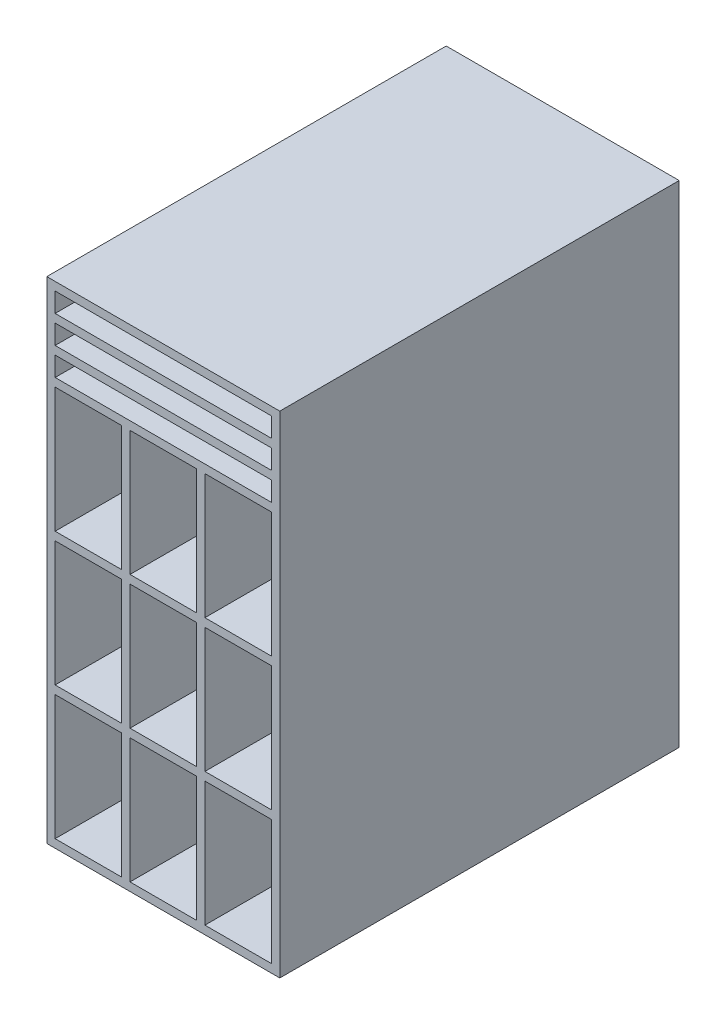
SolidWorks part; units mm, degrees
ref_plane "Front Plane" through (0, 0, 0) normal (0, 0, 1) x (1, 0, 0)
ref_plane "Top Plane" through (0, 0, 0) normal (0, 1, 0) x (1, 0, 0)
ref_plane "Right Plane" through (0, 0, 0) normal (1, 0, 0) x (0, 0, -1)
sketch "Sketch4" plane through (0, 0, 0) normal (0, 0, 1) x (1, 0, 0)
  line L1 (-177.8, -311.15) -> (177.8, -311.15)
  line L2 (-177.8, -311.15) -> (-177.8, 311.15)
  line L3 (-177.8, 311.15) -> (177.8, 311.15)
  line L4 (177.8, -311.15) -> (177.8, 311.15)
  line L5 (-177.8, -311.15) -> (177.8, 311.15) construction
  line L6 (-177.8, 311.15) -> (177.8, -311.15) construction
  point P0 (0, 0)
  dimension "D1" = 355.6
  dimension "D2" = 622.3
extrude "Boss-Extrude4" add sketch "Sketch4" along normal mid plane 190.5
shell "Shell1" thickness 12.7 removed face at (0, 0, 95.25)
sketch "Sketch5" plane through (0, 0, 95.25) normal (0, 0, 1) x (1, 0, 0)
  line L0 (-177.8, 304.8) -> (177.8, 304.8) construction
  line L1 (0, 101.6) -> (0, -101.6) construction
  line L2 (-177.8, 311.15) -> (-177.8, -311.15) construction
  line L3 (177.8, -311.15) -> (177.8, 311.15) construction
  line L6 (-177.8, -304.8) -> (177.8, -304.8) construction
  line L7 (-177.8, -311.15) -> (-177.8, -298.45) construction
  line L8 (-177.8, -311.15) -> (177.8, -311.15) construction
  line L9 (-165.1, -298.45) -> (165.1, -298.45) construction
  line L10 (-177.8, 298.45) -> (-177.8, 311.15) construction
  line L11 (165.1, 298.45) -> (-165.1, 298.45) construction
  line L12 (-171.45, -304.8) -> (-171.45, 304.8) construction
  line L13 (171.45, 304.8) -> (171.45, -304.8) construction
  line L14 (177.8, 0) -> (165.1, 0) construction
  line L15 (165.1, -298.45) -> (165.1, 298.45) construction
  line L16 (-165.1, 0) -> (-177.8, 0) construction
  line L17 (-165.1, 298.45) -> (-165.1, -298.45) construction
  line L18 (-57.15, 298.45) -> (-57.15, -298.45)
  line L19 (-165.1, -298.45) -> (165.1, -298.45) construction
  line L20 (57.15, 304.8) -> (57.15, -304.8)
  line L21 (-165.1, 101.6) -> (165.1, 101.6)
  line L22 (-165.1, -101.6) -> (165.1, -101.6)
  line L23 (-57.15, 0) -> (-171.45, 0) construction
  line L24 (-57.15, 0) -> (57.15, 0) construction
  line L25 (0, 304.8) -> (0, 101.6) construction
  point P11 (-177.8, -304.8)
  point P22 (-177.8, 304.8)
  point P30 (171.45, 0)
  point P34 (-171.45, 0)
  point P48 (0, 0)
  point P52 (0, 0)
rib "Rib1" sketch "Sketch5" sketch "Sketch5" thickness 12.7 extrusion direction normal to sketch draft on no parameters "D1"=12.7
sketch "Sketch8" plane through (0, 0, -95.25) normal (0, 0, -1) x (-1, 0, 0)
  line L4 (-177.8, -311.15) -> (177.8, -311.15)
  line L5 (177.8, -311.15) -> (177.8, 311.15)
  line L6 (177.8, 311.15) -> (-177.8, 311.15)
  line L7 (-177.8, 311.15) -> (-177.8, -311.15)
  line L8 (-177.8, -311.15) -> (177.8, -311.15)
  line L9 (177.8, -311.15) -> (177.8, 311.15)
  line L10 (177.8, 311.15) -> (-177.8, 311.15)
  line L11 (-177.8, 311.15) -> (-177.8, -311.15)
  dimension "D1" = 0
extrude "Boss-Extrude6" add sketch "Sketch8" along normal blind 76.2
shell "Shell4" thickness 12.7 removed face at (114.3, 298.45, 6.35)
sketch "Sketch9" plane through (0, 0, -171.45) normal (0, 0, -1) x (-1, 0, 0)
  line L0 (-177.8, 311.15) -> (-177.8, -311.15) construction
  line L3 (-165.1, 63.5) -> (165.1, 63.5)
  line L4 (-165.1, 63.5) -> (-165.1, -63.5)
  line L5 (-165.1, -63.5) -> (165.1, -63.5)
  line L6 (165.1, 63.5) -> (165.1, -63.5)
  line L8 (-165.1, -63.5) -> (165.1, 63.5) construction
  line L9 (-165.1, 63.5) -> (165.1, -63.5) construction
  point P10 (0, 0)
  dimension "D4" = 127
  dimension "D5" = 12.7
extrude "Cut-Extrude1" cut sketch "Sketch9" against normal blind 12.7
sketch "Sketch12" plane through (0, 0, -82.55) normal (0, 0, 1) x (1, 0, 0)
  line L2 (63.5, 241.3) -> (63.5, 165.1)
  line L4 (63.5, 298.45) -> (63.5, 107.95) construction
  arc A0 (63.5, 241.3) -> (63.5, 165.1) centre (63.5, 203.2) cw
  point P8 (63.5, 203.2)
  dimension "D1" = 38.1
extrude "Cut-Extrude3" cut sketch "Sketch12" against normal up to next
pattern_linear "LPattern1" count 3 spacing 114.3 along (-1, 0, 0) count 3 spacing 203.2 along (0, -1, 0) of "Cut-Extrude3"
sketch "Sketch16" plane through (-177.8, 0, 0) normal (1, 0, 0) x (0, 0, -1)
  line L0 (171.45, 311.15) -> (171.45, -311.15) construction
  line L1 (-95.25, -311.15) -> (171.45, -311.15) construction
  circle A0 centre (120.65, -260.35) radius 25.4
  dimension "D3" = 50.8
  dimension "D1" = 50.8
  dimension "D2" = 50.8
extrude "Cut-Extrude5" cut sketch "Sketch16" along normal up to next
sketch "Sketch6" plane through (0, 311.15, 0) normal (0, 1, 0) x (1, 0, 0)
  line L4 (-177.8, 171.45) -> (-177.8, -95.25)
  line L5 (-177.8, -95.25) -> (177.8, -95.25)
  line L6 (177.8, -95.25) -> (177.8, 171.45)
  line L7 (177.8, 171.45) -> (-177.8, 171.45)
  line L8 (-177.8, 171.45) -> (-177.8, -95.25)
  line L9 (-177.8, -95.25) -> (177.8, -95.25)
  line L10 (177.8, -95.25) -> (177.8, 171.45)
  line L12 (177.8, 171.45) -> (-177.8, 171.45)
  dimension "D1" = 0
extrude "Boss-Extrude5" add sketch "Sketch6" along normal blind 127
sketch "Sketch10" plane through (0, 0, 95.25) normal (0, 0, 1) x (1, 0, 0)
  line L0 (-177.8, 438.15) -> (177.8, 438.15) construction
  line L1 (-165.1, 425.45) -> (165.1, 425.45)
  line L2 (-165.1, 425.45) -> (-165.1, 311.15)
  line L3 (-165.1, 311.15) -> (165.1, 311.15)
  line L4 (165.1, 425.45) -> (165.1, 311.15)
  line L5 (-177.8, 438.15) -> (-177.8, -311.15) construction
  line L6 (177.8, -311.15) -> (177.8, 438.15) construction
  line L7 (165.1, 298.45) -> (63.5, 298.45) construction
  dimension "D1" = 12.7
  dimension "D2" = 12.7
  dimension "D3" = 12.7
  dimension "D4" = 12.7
extrude "Cut-Extrude2" cut sketch "Sketch10" against normal offset from surface (254 mm away) 12.7 up to face at (0, 0, -171.45)
sketch "Sketch13" plane through (0, 0, 95.25) normal (0, 0, 1) x (1, 0, 0)
  line L0 (-177.8, 431.8) -> (177.8, 431.8) construction
  line L1 (-177.8, 438.15) -> (-177.8, -311.15) construction
  line L2 (177.8, -311.15) -> (177.8, 438.15) construction
  line L3 (-177.8, 304.8) -> (177.8, 304.8) construction
  line L4 (-177.8, 298.45) -> (-177.8, 311.15) construction
  line L5 (-165.1, 311.15) -> (165.1, 311.15) construction
  line L6 (-63.5, 298.45) -> (-165.1, 298.45) construction
  line L7 (-177.8, 425.45) -> (-177.8, 438.15) construction
  line L8 (-177.8, 438.15) -> (177.8, 438.15) construction
  line L9 (165.1, 425.45) -> (-165.1, 425.45) construction
  line L10 (-165.1, 389.4667) -> (165.1, 389.4667)
  line L11 (-165.1, 425.45) -> (-165.1, 311.15) construction
  line L12 (165.1, 311.15) -> (165.1, 425.45) construction
  line L13 (-165.1, 347.1333) -> (165.1, 347.1333)
  line L14 (-165.1, 425.45) -> (-165.1, 311.15) construction
  line L15 (165.1, 311.15) -> (165.1, 425.45) construction
  line L16 (0, 431.8) -> (0, 389.4667) construction
  line L17 (0, 389.4667) -> (0, 347.1333) construction
  line L18 (0, 347.1333) -> (0, 304.8) construction
  point P11 (-177.8, 304.8)
  point P20 (-177.8, 431.8)
rib "Rib3" sketch "Sketch13" sketch "Sketch13" thickness 12.7 extrusion direction normal to sketch draft on no parameters "D1"=12.7
sketch "Sketch14" plane through (0, 395.8167, 0) normal (0, 1, 0) x (1, 0, 0)
  line L0 (-165.1, 158.75) -> (165.1, 158.75) construction
  line L1 (165.1, -95.25) -> (165.1, 158.75) construction
  circle A0 centre (139.7, 133.35) radius 19.05
  dimension "D3" = 38.1
  dimension "D1" = 25.4
  dimension "D2" = 25.4
extrude "Cut-Extrude4" cut sketch "Sketch14" against normal up to surface (97.3667 mm away)
sketch "Sketch15" plane through (0, 0, -171.45) normal (0, 0, -1) x (-1, 0, 0)
  line L1 (-177.8, 438.15) -> (177.8, 438.15)
  line L2 (-177.8, 438.15) -> (-177.8, -311.15)
  line L3 (-177.8, -311.15) -> (177.8, -311.15)
  line L4 (177.8, 438.15) -> (177.8, -311.15)
extrude "Boss-Extrude7" add sketch "Sketch15" along normal blind 342.9
sketch "Sketch17" plane through (-177.8, 0, 0) normal (-1, 0, 0) x (0, 0, 1)
  line L0 (-171.45, 63.5) -> (-171.45, -63.5) construction
  line L1 (-501.65, 425.45) -> (-171.45, 425.45)
  line L2 (-501.65, 425.45) -> (-501.65, -298.45)
  line L3 (-501.65, -298.45) -> (-171.45, -298.45)
  line L4 (-171.45, 425.45) -> (-171.45, -298.45)
  line L5 (-95.25, -298.45) -> (-158.75, -298.45) construction
  line L6 (-158.75, 425.45) -> (95.25, 425.45) construction
  line L7 (-514.35, -311.15) -> (-514.35, 438.15) construction
  dimension "D1" = 12.7
extrude "Cut-Extrude6" cut sketch "Sketch17" against normal offset from surface (342.9 mm away) 12.7 up to face at (177.8, 63.5, -209.55)
